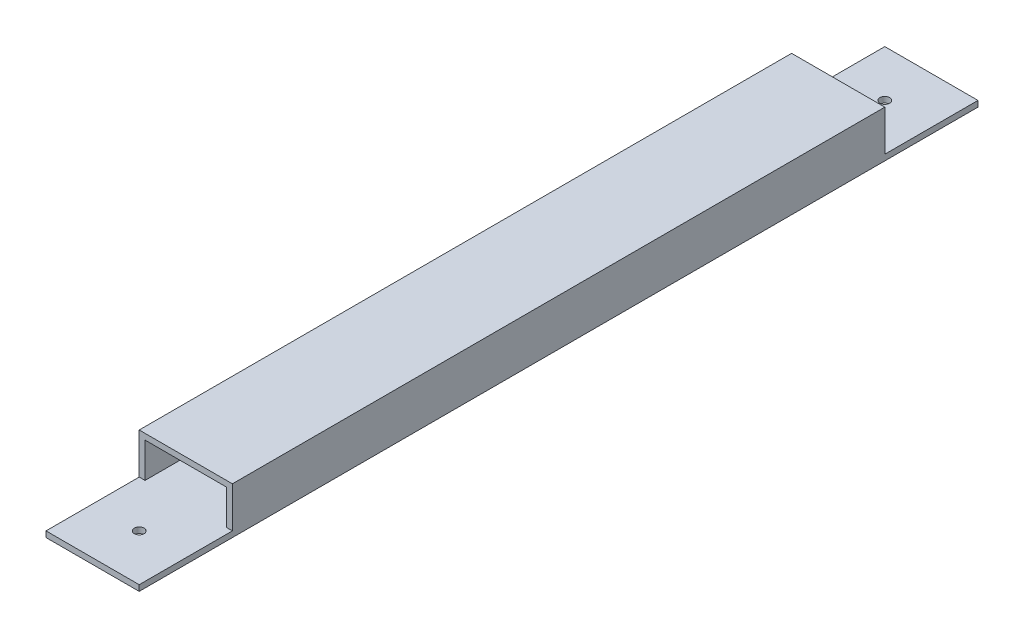
SolidWorks part; units mm, degrees
ref_plane "Front Plane" through (0, 0, 0) normal (0, 0, 1) x (1, 0, 0)
ref_plane "Top Plane" through (0, 0, 0) normal (0, 1, 0) x (1, 0, 0)
ref_plane "Right Plane" through (0, 0, 0) normal (1, 0, 0) x (0, 0, -1)
sketch "Sketch1" plane through (0, 0, 0) normal (0, 0, 1) x (1, 0, 0)
  line L0 (-22.225, -9.525) -> (22.225, -9.525)
  line L1 (-25.4, -12.7) -> (25.4, -12.7)
  line L2 (-25.4, -12.7) -> (-25.4, 12.7)
  line L3 (-25.4, 12.7) -> (25.4, 12.7)
  line L4 (25.4, -12.7) -> (25.4, 12.7)
  line L5 (22.225, -9.525) -> (22.225, 9.525)
  line L6 (-22.225, 9.525) -> (22.225, 9.525)
  line L7 (-22.225, -9.525) -> (-22.225, 9.525)
  dimension "D1" = 25.4
  dimension "D2" = 50.8
  dimension "D3" = 3.175
extrude "Boss-Extrude1" add sketch "Sketch1" along normal blind 457.2
sketch "Sketch2" plane through (0, 12.7, 0) normal (0, 1, 0) x (1, 0, 0)
  line L0 (0, -457.2) -> (0, -431.8) construction
  line L1 (25.4, -457.2) -> (-25.4, -457.2) construction
  line L2 (0, -431.8) -> (0, -25.4) construction
  line L3 (0, -25.4) -> (0, 0) construction
  line L4 (25.4, 0) -> (-25.4, 0) construction
  circle A0 centre (0, -431.8) radius 2.667
  circle A1 centre (0, -25.4) radius 2.667
  dimension "D2" = 5.334
  dimension "D1" = 406.4
extrude "Cut-Extrude1" cut sketch "Sketch2" against normal through all
sketch "Sketch3" plane through (0, 12.7, 0) normal (0, 1, 0) x (1, 0, 0)
  line L0 (25.4, -457.2) -> (25.4, 0) construction
  line L1 (-25.4, -457.2) -> (25.4, -457.2)
  line L2 (-25.4, -457.2) -> (-25.4, -406.4)
  line L3 (-25.4, -406.4) -> (25.4, -406.4)
  line L4 (25.4, -457.2) -> (25.4, -406.4)
  line L5 (-25.4, -457.2) -> (25.4, -406.4) construction
  line L6 (-25.4, -406.4) -> (25.4, -457.2) construction
  line L8 (-25.4, 0) -> (25.4, 0)
  line L9 (-25.4, 0) -> (-25.4, -50.8)
  line L10 (-25.4, -50.8) -> (25.4, -50.8)
  line L11 (25.4, 0) -> (25.4, -50.8)
  line L12 (-25.4, 0) -> (25.4, -50.8) construction
  line L13 (-25.4, -50.8) -> (25.4, 0) construction
  point P4 (0, -431.8)
  point P12 (0, -25.4)
  dimension "D1" = 50.8
extrude "Cut-Extrude2" cut sketch "Sketch3" against normal up to surface (22.225 mm away) up to face at (0, -9.525, 434.467)
